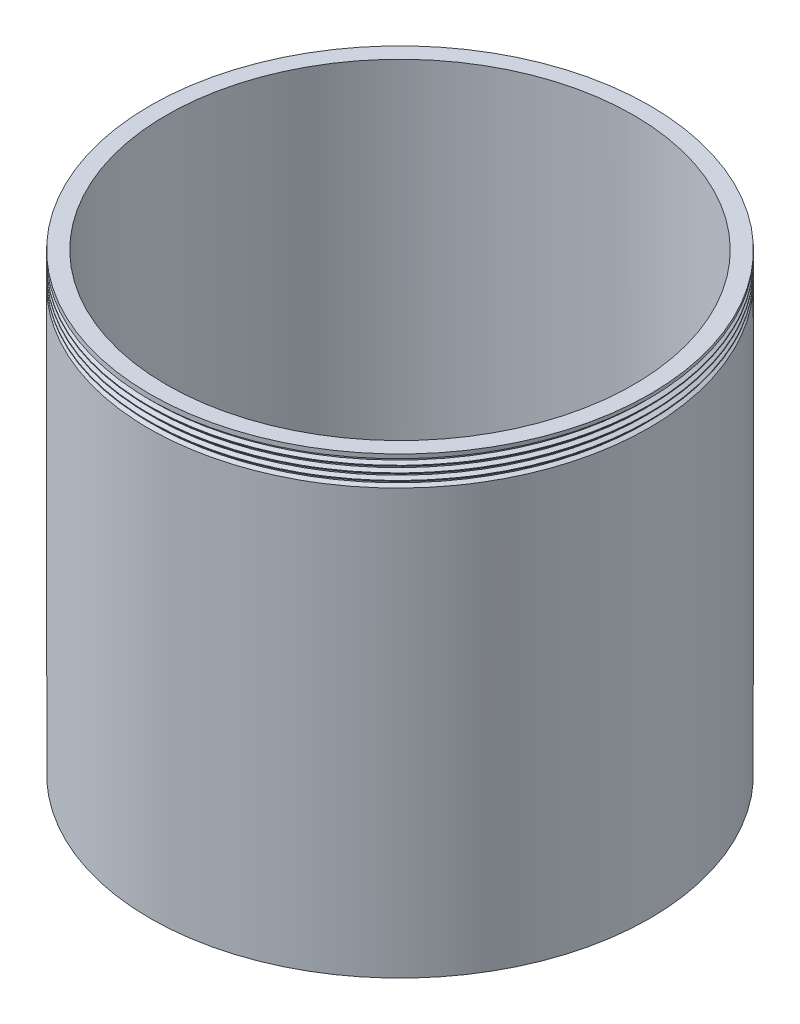
SolidWorks part; units mm, degrees
material "1060 Alloy"
ref_plane "Front Plane" through (0, 0, 0) normal (0, 0, 1) x (1, 0, 0)
ref_plane "Top Plane" through (0, 0, 0) normal (0, 1, 0) x (1, 0, 0)
ref_plane "Right Plane" through (0, 0, 0) normal (1, 0, 0) x (0, 0, -1)
sketch "Sketch1" plane through (0, 0, 0) normal (0, 1, 0) x (1, 0, 0)
  circle A0 centre (0, 0) radius 8.9
  circle A1 centre (0, 0) radius 9.525
  dimension "D1" = 17.8
  dimension "D2" = 19.05
extrude "Boss-Extrude1" add sketch "Sketch1" along normal blind 17.3
thread "Thread1" pitch 0.25 method cut profile "Thread Profile1" start angle 0, offset 0, length 1, pitch 0.25, diameter 19.05
ref_plane "Plane1" through (-9.525, 17.3, 0) normal (0, 0, 1) x (-1, 0, 0)
sketch "Thread Profile1" plane through (-9.525, 17.3, 0) normal (0, 0, 1) x (-1, 0, 0)
  line L0 (0, 0) -> (0, 0.25) construction
  line L11 (0, 0) -> (0, 0.2187)
  line L12 (0, 0.2187) -> (-0.1353, 0.1406)
  line L13 (-0.1353, 0.1406) -> (-0.1353, 0.0781)
  line L15 (-0.1353, 0.0781) -> (0, 0)
  line L17 (-0.1353, 0.1094) -> (0, 0.1094) construction
  point P2 (0, 0)
  dimension "Pitch" = 0.25
  dimension "Profile_Angle" = 60
  dimension "Profile_Land" = 0.0625
  dimension "Profile_Height" = 0.1353
thread "Thread2" pitch 0.25 method extrude profile "Thread Profile2" start angle 0, offset 0, length 0.8, pitch 0.25, diameter 17.8
ref_plane "Plane2" through (8.9, 0, 0) normal (0, 0, 1) x (1, 0, 0)
sketch "Thread Profile2" plane through (8.9, 0, 0) normal (0, 0, 1) x (1, 0, 0)
  line L0 (0, 0) -> (0, 0.25) construction
  line L11 (0, 0) -> (0, 0.2187)
  line L12 (0, 0.2187) -> (-0.1353, 0.1406)
  line L13 (-0.1353, 0.1406) -> (-0.1353, 0.0781)
  line L15 (-0.1353, 0.0781) -> (0, 0)
  line L17 (-0.1353, 0.1094) -> (0, 0.1094) construction
  point P2 (0, 0)
  dimension "Pitch" = 0.25
  dimension "Profile_Angle" = 60
  dimension "Profile_Land" = 0.0625
  dimension "Profile_Height" = 0.1353
